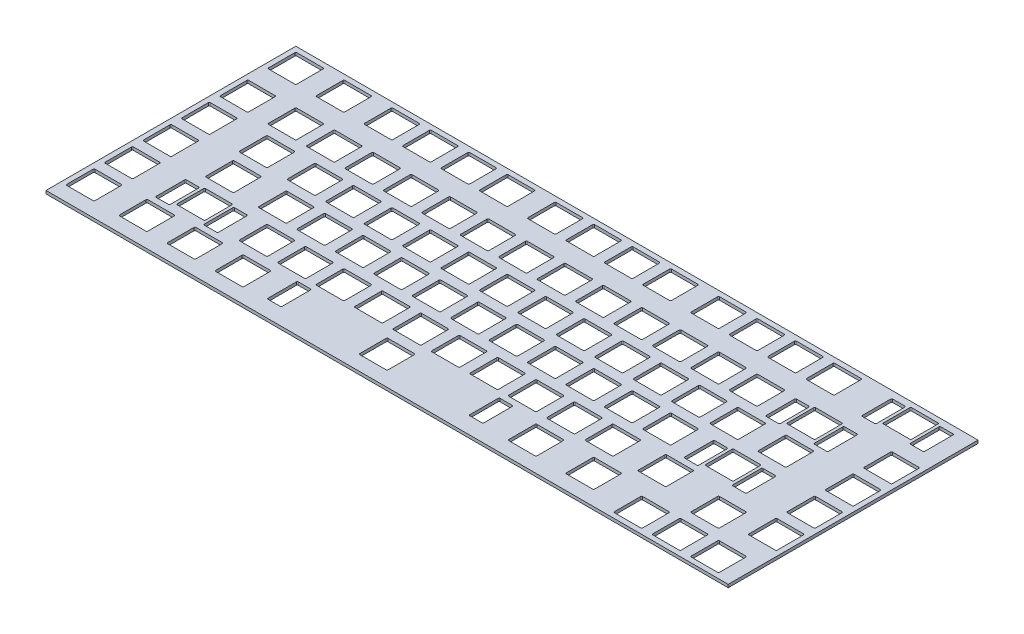
SolidWorks part; units mm, degrees
ref_plane "Front" through (0, 0, 0) normal (0, 0, 1) x (1, 0, 0)
ref_plane "Top" through (0, 0, 0) normal (0, 1, 0) x (1, 0, 0)
ref_plane "Right" through (0, 0, 0) normal (1, 0, 0) x (0, 0, -1)
sketch "Sketch1" plane through (0, 0, 0) normal (0, 1, 0) x (1, 0, 0)
  line L0 (3.025, -2.525) -> (16.025, -2.525)
  line L1 (3.025, -16.525) -> (16.025, -16.525)
  line L2 (2.525, -3.025) -> (2.525, -16.025)
  line L3 (16.525, -3.025) -> (16.525, -16.025)
  line L4 (26.8375, -2.525) -> (39.8375, -2.525)
  line L5 (26.8375, -16.525) -> (39.8375, -16.525)
  line L6 (26.3375, -3.025) -> (26.3375, -16.025)
  line L7 (40.3375, -3.025) -> (40.3375, -16.025)
  line L8 (50.65, -2.525) -> (63.65, -2.525)
  line L9 (50.65, -16.525) -> (63.65, -16.525)
  line L10 (50.15, -3.025) -> (50.15, -16.025)
  line L11 (64.15, -3.025) -> (64.15, -16.025)
  line L12 (69.7, -2.525) -> (82.7, -2.525)
  line L13 (69.7, -16.525) -> (82.7, -16.525)
  line L14 (69.2, -3.025) -> (69.2, -16.025)
  line L15 (83.2, -3.025) -> (83.2, -16.025)
  line L16 (88.75, -2.525) -> (101.75, -2.525)
  line L17 (88.75, -16.525) -> (101.75, -16.525)
  line L18 (88.25, -3.025) -> (88.25, -16.025)
  line L19 (102.25, -3.025) -> (102.25, -16.025)
  line L20 (107.8, -2.525) -> (120.8, -2.525)
  line L21 (107.8, -16.525) -> (120.8, -16.525)
  line L22 (107.3, -3.025) -> (107.3, -16.025)
  line L23 (121.3, -3.025) -> (121.3, -16.025)
  line L24 (131.6125, -2.525) -> (144.6125, -2.525)
  line L25 (131.6125, -16.525) -> (144.6125, -16.525)
  line L26 (131.1125, -3.025) -> (131.1125, -16.025)
  line L27 (145.1125, -3.025) -> (145.1125, -16.025)
  line L28 (150.6625, -2.525) -> (163.6625, -2.525)
  line L29 (150.6625, -16.525) -> (163.6625, -16.525)
  line L30 (150.1625, -3.025) -> (150.1625, -16.025)
  line L31 (164.1625, -3.025) -> (164.1625, -16.025)
  line L32 (169.7125, -2.525) -> (182.7125, -2.525)
  line L33 (169.7125, -16.525) -> (182.7125, -16.525)
  line L34 (169.2125, -3.025) -> (169.2125, -16.025)
  line L35 (183.2125, -3.025) -> (183.2125, -16.025)
  line L36 (188.7625, -2.525) -> (201.7625, -2.525)
  line L37 (188.7625, -16.525) -> (201.7625, -16.525)
  line L38 (188.2625, -3.025) -> (188.2625, -16.025)
  line L39 (202.2625, -3.025) -> (202.2625, -16.025)
  line L40 (212.575, -2.525) -> (225.575, -2.525)
  line L41 (212.575, -16.525) -> (225.575, -16.525)
  line L42 (212.075, -3.025) -> (212.075, -16.025)
  line L43 (226.075, -3.025) -> (226.075, -16.025)
  line L44 (231.625, -2.525) -> (244.625, -2.525)
  line L45 (231.625, -16.525) -> (244.625, -16.525)
  line L46 (231.125, -3.025) -> (231.125, -16.025)
  line L47 (245.125, -3.025) -> (245.125, -16.025)
  line L48 (250.675, -2.525) -> (263.675, -2.525)
  line L49 (250.675, -16.525) -> (263.675, -16.525)
  line L50 (250.175, -3.025) -> (250.175, -16.025)
  line L51 (264.175, -3.025) -> (264.175, -16.025)
  line L52 (269.725, -2.525) -> (282.725, -2.525)
  line L53 (269.725, -16.525) -> (282.725, -16.525)
  line L54 (269.225, -3.025) -> (269.225, -16.025)
  line L55 (283.225, -3.025) -> (283.225, -16.025)
  line L56 (307.825, -2.525) -> (320.825, -2.525)
  line L57 (307.825, -16.525) -> (320.825, -16.525)
  line L58 (307.325, -3.025) -> (307.325, -16.025)
  line L59 (321.325, -3.025) -> (321.325, -16.025)
  line L60 (299.387, -3.525) -> (305.387, -3.525)
  line L61 (299.387, -18.525) -> (305.387, -18.525)
  line L62 (298.887, -4.025) -> (298.887, -18.025)
  line L63 (305.887, -4.025) -> (305.887, -18.025)
  line L64 (323.263, -3.525) -> (329.263, -3.525)
  line L65 (323.263, -18.525) -> (329.263, -18.525)
  line L66 (322.763, -4.025) -> (322.763, -18.025)
  line L67 (329.763, -4.025) -> (329.763, -18.025)
  line L68 (3.025, -26.3375) -> (16.025, -26.3375)
  line L69 (3.025, -40.3375) -> (16.025, -40.3375)
  line L70 (2.525, -26.8375) -> (2.525, -39.8375)
  line L71 (16.525, -26.8375) -> (16.525, -39.8375)
  line L72 (26.8375, -26.3375) -> (39.8375, -26.3375)
  line L73 (26.8375, -40.3375) -> (39.8375, -40.3375)
  line L74 (26.3375, -26.8375) -> (26.3375, -39.8375)
  line L75 (40.3375, -26.8375) -> (40.3375, -39.8375)
  line L76 (45.8875, -26.3375) -> (58.8875, -26.3375)
  line L77 (45.8875, -40.3375) -> (58.8875, -40.3375)
  line L78 (45.3875, -26.8375) -> (45.3875, -39.8375)
  line L79 (59.3875, -26.8375) -> (59.3875, -39.8375)
  line L80 (64.9375, -26.3375) -> (77.9375, -26.3375)
  line L81 (64.9375, -40.3375) -> (77.9375, -40.3375)
  line L82 (64.4375, -26.8375) -> (64.4375, -39.8375)
  line L83 (78.4375, -26.8375) -> (78.4375, -39.8375)
  line L84 (83.9875, -26.3375) -> (96.9875, -26.3375)
  line L85 (83.9875, -40.3375) -> (96.9875, -40.3375)
  line L86 (83.4875, -26.8375) -> (83.4875, -39.8375)
  line L87 (97.4875, -26.8375) -> (97.4875, -39.8375)
  line L88 (103.0375, -26.3375) -> (116.0375, -26.3375)
  line L89 (103.0375, -40.3375) -> (116.0375, -40.3375)
  line L90 (102.5375, -26.8375) -> (102.5375, -39.8375)
  line L91 (116.5375, -26.8375) -> (116.5375, -39.8375)
  line L92 (122.0875, -26.3375) -> (135.0875, -26.3375)
  line L93 (122.0875, -40.3375) -> (135.0875, -40.3375)
  line L94 (121.5875, -26.8375) -> (121.5875, -39.8375)
  line L95 (135.5875, -26.8375) -> (135.5875, -39.8375)
  line L96 (141.1375, -26.3375) -> (154.1375, -26.3375)
  line L97 (141.1375, -40.3375) -> (154.1375, -40.3375)
  line L98 (140.6375, -26.8375) -> (140.6375, -39.8375)
  line L99 (154.6375, -26.8375) -> (154.6375, -39.8375)
  line L100 (160.1875, -26.3375) -> (173.1875, -26.3375)
  line L101 (160.1875, -40.3375) -> (173.1875, -40.3375)
  line L102 (159.6875, -26.8375) -> (159.6875, -39.8375)
  line L103 (173.6875, -26.8375) -> (173.6875, -39.8375)
  line L104 (179.2375, -26.3375) -> (192.2375, -26.3375)
  line L105 (179.2375, -40.3375) -> (192.2375, -40.3375)
  line L106 (178.7375, -26.8375) -> (178.7375, -39.8375)
  line L107 (192.7375, -26.8375) -> (192.7375, -39.8375)
  line L108 (198.2875, -26.3375) -> (211.2875, -26.3375)
  line L109 (198.2875, -40.3375) -> (211.2875, -40.3375)
  line L110 (197.7875, -26.8375) -> (197.7875, -39.8375)
  line L111 (211.7875, -26.8375) -> (211.7875, -39.8375)
  line L112 (217.3375, -26.3375) -> (230.3375, -26.3375)
  line L113 (217.3375, -40.3375) -> (230.3375, -40.3375)
  line L114 (216.8375, -26.8375) -> (216.8375, -39.8375)
  line L115 (230.8375, -26.8375) -> (230.8375, -39.8375)
  line L116 (236.3875, -26.3375) -> (249.3875, -26.3375)
  line L117 (236.3875, -40.3375) -> (249.3875, -40.3375)
  line L118 (235.8875, -26.8375) -> (235.8875, -39.8375)
  line L119 (249.8875, -26.8375) -> (249.8875, -39.8375)
  line L120 (255.4375, -26.3375) -> (268.4375, -26.3375)
  line L121 (255.4375, -40.3375) -> (268.4375, -40.3375)
  line L122 (254.9375, -26.8375) -> (254.9375, -39.8375)
  line L123 (268.9375, -26.8375) -> (268.9375, -39.8375)
  line L124 (284.0125, -26.3375) -> (297.0125, -26.3375)
  line L125 (284.0125, -40.3375) -> (297.0125, -40.3375)
  line L126 (283.5125, -26.8375) -> (283.5125, -39.8375)
  line L127 (297.5125, -26.8375) -> (297.5125, -39.8375)
  line L128 (275.5745, -27.3375) -> (281.5745, -27.3375)
  line L129 (275.5745, -42.3375) -> (281.5745, -42.3375)
  line L130 (275.0745, -27.8375) -> (275.0745, -41.8375)
  line L131 (282.0745, -27.8375) -> (282.0745, -41.8375)
  line L132 (299.4505, -27.3375) -> (305.4505, -27.3375)
  line L133 (299.4505, -42.3375) -> (305.4505, -42.3375)
  line L134 (298.9505, -27.8375) -> (298.9505, -41.8375)
  line L135 (305.9505, -27.8375) -> (305.9505, -41.8375)
  line L136 (322.1125, -26.3375) -> (335.1125, -26.3375)
  line L137 (322.1125, -40.3375) -> (335.1125, -40.3375)
  line L138 (321.6125, -26.8375) -> (321.6125, -39.8375)
  line L139 (335.6125, -26.8375) -> (335.6125, -39.8375)
  line L140 (3.025, -45.3875) -> (16.025, -45.3875)
  line L141 (3.025, -59.3875) -> (16.025, -59.3875)
  line L142 (2.525, -45.8875) -> (2.525, -58.8875)
  line L143 (16.525, -45.8875) -> (16.525, -58.8875)
  line L144 (31.6, -45.3875) -> (44.6, -45.3875)
  line L145 (31.6, -59.3875) -> (44.6, -59.3875)
  line L146 (31.1, -45.8875) -> (31.1, -58.8875)
  line L147 (45.1, -45.8875) -> (45.1, -58.8875)
  line L148 (55.4125, -45.3875) -> (68.4125, -45.3875)
  line L149 (55.4125, -59.3875) -> (68.4125, -59.3875)
  line L150 (54.9125, -45.8875) -> (54.9125, -58.8875)
  line L151 (68.9125, -45.8875) -> (68.9125, -58.8875)
  line L152 (74.4625, -45.3875) -> (87.4625, -45.3875)
  line L153 (74.4625, -59.3875) -> (87.4625, -59.3875)
  line L154 (73.9625, -45.8875) -> (73.9625, -58.8875)
  line L155 (87.9625, -45.8875) -> (87.9625, -58.8875)
  line L156 (93.5125, -45.3875) -> (106.5125, -45.3875)
  line L157 (93.5125, -59.3875) -> (106.5125, -59.3875)
  line L158 (93.0125, -45.8875) -> (93.0125, -58.8875)
  line L159 (107.0125, -45.8875) -> (107.0125, -58.8875)
  line L160 (112.5625, -45.3875) -> (125.5625, -45.3875)
  line L161 (112.5625, -59.3875) -> (125.5625, -59.3875)
  line L162 (112.0625, -45.8875) -> (112.0625, -58.8875)
  line L163 (126.0625, -45.8875) -> (126.0625, -58.8875)
  line L164 (131.6125, -45.3875) -> (144.6125, -45.3875)
  line L165 (131.6125, -59.3875) -> (144.6125, -59.3875)
  line L166 (131.1125, -45.8875) -> (131.1125, -58.8875)
  line L167 (145.1125, -45.8875) -> (145.1125, -58.8875)
  line L168 (150.6625, -45.3875) -> (163.6625, -45.3875)
  line L169 (150.6625, -59.3875) -> (163.6625, -59.3875)
  line L170 (150.1625, -45.8875) -> (150.1625, -58.8875)
  line L171 (164.1625, -45.8875) -> (164.1625, -58.8875)
  line L172 (169.7125, -45.3875) -> (182.7125, -45.3875)
  line L173 (169.7125, -59.3875) -> (182.7125, -59.3875)
  line L174 (169.2125, -45.8875) -> (169.2125, -58.8875)
  line L175 (183.2125, -45.8875) -> (183.2125, -58.8875)
  line L176 (188.7625, -45.3875) -> (201.7625, -45.3875)
  line L177 (188.7625, -59.3875) -> (201.7625, -59.3875)
  line L178 (188.2625, -45.8875) -> (188.2625, -58.8875)
  line L179 (202.2625, -45.8875) -> (202.2625, -58.8875)
  line L180 (207.8125, -45.3875) -> (220.8125, -45.3875)
  line L181 (207.8125, -59.3875) -> (220.8125, -59.3875)
  line L182 (207.3125, -45.8875) -> (207.3125, -58.8875)
  line L183 (221.3125, -45.8875) -> (221.3125, -58.8875)
  line L184 (226.8625, -45.3875) -> (239.8625, -45.3875)
  line L185 (226.8625, -59.3875) -> (239.8625, -59.3875)
  line L186 (226.3625, -45.8875) -> (226.3625, -58.8875)
  line L187 (240.3625, -45.8875) -> (240.3625, -58.8875)
  line L188 (245.9125, -45.3875) -> (258.9125, -45.3875)
  line L189 (245.9125, -59.3875) -> (258.9125, -59.3875)
  line L190 (245.4125, -45.8875) -> (245.4125, -58.8875)
  line L191 (259.4125, -45.8875) -> (259.4125, -58.8875)
  line L192 (264.9625, -45.3875) -> (277.9625, -45.3875)
  line L193 (264.9625, -59.3875) -> (277.9625, -59.3875)
  line L194 (264.4625, -45.8875) -> (264.4625, -58.8875)
  line L195 (278.4625, -45.8875) -> (278.4625, -58.8875)
  line L196 (288.775, -45.3875) -> (301.775, -45.3875)
  line L197 (288.775, -59.3875) -> (301.775, -59.3875)
  line L198 (288.275, -45.8875) -> (288.275, -58.8875)
  line L199 (302.275, -45.8875) -> (302.275, -58.8875)
  line L200 (322.1125, -45.3875) -> (335.1125, -45.3875)
  line L201 (322.1125, -59.3875) -> (335.1125, -59.3875)
  line L202 (321.6125, -45.8875) -> (321.6125, -58.8875)
  line L203 (335.6125, -45.8875) -> (335.6125, -58.8875)
  line L204 (3.025, -64.4375) -> (16.025, -64.4375)
  line L205 (3.025, -78.4375) -> (16.025, -78.4375)
  line L206 (2.525, -64.9375) -> (2.525, -77.9375)
  line L207 (16.525, -64.9375) -> (16.525, -77.9375)
  line L208 (33.9813, -64.4375) -> (46.9813, -64.4375)
  line L209 (33.9813, -78.4375) -> (46.9813, -78.4375)
  line L210 (33.4813, -64.9375) -> (33.4813, -77.9375)
  line L211 (47.4813, -64.9375) -> (47.4813, -77.9375)
  line L212 (60.175, -64.4375) -> (73.175, -64.4375)
  line L213 (60.175, -78.4375) -> (73.175, -78.4375)
  line L214 (59.675, -64.9375) -> (59.675, -77.9375)
  line L215 (73.675, -64.9375) -> (73.675, -77.9375)
  line L216 (79.225, -64.4375) -> (92.225, -64.4375)
  line L217 (79.225, -78.4375) -> (92.225, -78.4375)
  line L218 (78.725, -64.9375) -> (78.725, -77.9375)
  line L219 (92.725, -64.9375) -> (92.725, -77.9375)
  line L220 (98.275, -64.4375) -> (111.275, -64.4375)
  line L221 (98.275, -78.4375) -> (111.275, -78.4375)
  line L222 (97.775, -64.9375) -> (97.775, -77.9375)
  line L223 (111.775, -64.9375) -> (111.775, -77.9375)
  line L224 (117.325, -64.4375) -> (130.325, -64.4375)
  line L225 (117.325, -78.4375) -> (130.325, -78.4375)
  line L226 (116.825, -64.9375) -> (116.825, -77.9375)
  line L227 (130.825, -64.9375) -> (130.825, -77.9375)
  line L228 (136.375, -64.4375) -> (149.375, -64.4375)
  line L229 (136.375, -78.4375) -> (149.375, -78.4375)
  line L230 (135.875, -64.9375) -> (135.875, -77.9375)
  line L231 (149.875, -64.9375) -> (149.875, -77.9375)
  line L232 (155.425, -64.4375) -> (168.425, -64.4375)
  line L233 (155.425, -78.4375) -> (168.425, -78.4375)
  line L234 (154.925, -64.9375) -> (154.925, -77.9375)
  line L235 (168.925, -64.9375) -> (168.925, -77.9375)
  line L236 (174.475, -64.4375) -> (187.475, -64.4375)
  line L237 (174.475, -78.4375) -> (187.475, -78.4375)
  line L238 (173.975, -64.9375) -> (173.975, -77.9375)
  line L239 (187.975, -64.9375) -> (187.975, -77.9375)
  line L240 (193.525, -64.4375) -> (206.525, -64.4375)
  line L241 (193.525, -78.4375) -> (206.525, -78.4375)
  line L242 (193.025, -64.9375) -> (193.025, -77.9375)
  line L243 (207.025, -64.9375) -> (207.025, -77.9375)
  line L244 (212.575, -64.4375) -> (225.575, -64.4375)
  line L245 (212.575, -78.4375) -> (225.575, -78.4375)
  line L246 (212.075, -64.9375) -> (212.075, -77.9375)
  line L247 (226.075, -64.9375) -> (226.075, -77.9375)
  line L248 (231.625, -64.4375) -> (244.625, -64.4375)
  line L249 (231.625, -78.4375) -> (244.625, -78.4375)
  line L250 (231.125, -64.9375) -> (231.125, -77.9375)
  line L251 (245.125, -64.9375) -> (245.125, -77.9375)
  line L252 (250.675, -64.4375) -> (263.675, -64.4375)
  line L253 (250.675, -78.4375) -> (263.675, -78.4375)
  line L254 (250.175, -64.9375) -> (250.175, -77.9375)
  line L255 (264.175, -64.9375) -> (264.175, -77.9375)
  line L256 (281.6313, -64.4375) -> (294.6313, -64.4375)
  line L257 (281.6313, -78.4375) -> (294.6313, -78.4375)
  line L258 (281.1313, -64.9375) -> (281.1313, -77.9375)
  line L259 (295.1313, -64.9375) -> (295.1313, -77.9375)
  line L260 (273.1932, -65.4375) -> (279.1932, -65.4375)
  line L261 (273.1932, -80.4375) -> (279.1932, -80.4375)
  line L262 (272.6932, -65.9375) -> (272.6932, -79.9375)
  line L263 (279.6932, -65.9375) -> (279.6932, -79.9375)
  line L264 (297.0693, -65.4375) -> (303.0693, -65.4375)
  line L265 (297.0693, -80.4375) -> (303.0693, -80.4375)
  line L266 (296.5693, -65.9375) -> (296.5693, -79.9375)
  line L267 (303.5693, -65.9375) -> (303.5693, -79.9375)
  line L268 (322.1125, -64.4375) -> (335.1125, -64.4375)
  line L269 (322.1125, -78.4375) -> (335.1125, -78.4375)
  line L270 (321.6125, -64.9375) -> (321.6125, -77.9375)
  line L271 (335.6125, -64.9375) -> (335.6125, -77.9375)
  line L272 (3.025, -83.4875) -> (16.025, -83.4875)
  line L273 (3.025, -97.4875) -> (16.025, -97.4875)
  line L274 (2.525, -83.9875) -> (2.525, -96.9875)
  line L275 (16.525, -83.9875) -> (16.525, -96.9875)
  line L276 (38.7437, -83.4875) -> (51.7437, -83.4875)
  line L277 (38.7437, -97.4875) -> (51.7437, -97.4875)
  line L278 (38.2437, -83.9875) -> (38.2437, -96.9875)
  line L279 (52.2437, -83.9875) -> (52.2437, -96.9875)
  line L280 (30.3057, -84.4875) -> (36.3058, -84.4875)
  line L281 (30.3057, -99.4875) -> (36.3058, -99.4875)
  line L282 (29.8057, -84.9875) -> (29.8057, -98.9875)
  line L283 (36.8058, -84.9875) -> (36.8058, -98.9875)
  line L284 (54.1818, -84.4875) -> (60.1818, -84.4875)
  line L285 (54.1818, -99.4875) -> (60.1818, -99.4875)
  line L286 (53.6818, -84.9875) -> (53.6818, -98.9875)
  line L287 (60.6818, -84.9875) -> (60.6818, -98.9875)
  line L288 (69.7, -83.4875) -> (82.7, -83.4875)
  line L289 (69.7, -97.4875) -> (82.7, -97.4875)
  line L290 (69.2, -83.9875) -> (69.2, -96.9875)
  line L291 (83.2, -83.9875) -> (83.2, -96.9875)
  line L292 (88.75, -83.4875) -> (101.75, -83.4875)
  line L293 (88.75, -97.4875) -> (101.75, -97.4875)
  line L294 (88.25, -83.9875) -> (88.25, -96.9875)
  line L295 (102.25, -83.9875) -> (102.25, -96.9875)
  line L296 (107.8, -83.4875) -> (120.8, -83.4875)
  line L297 (107.8, -97.4875) -> (120.8, -97.4875)
  line L298 (107.3, -83.9875) -> (107.3, -96.9875)
  line L299 (121.3, -83.9875) -> (121.3, -96.9875)
  line L300 (126.85, -83.4875) -> (139.85, -83.4875)
  line L301 (126.85, -97.4875) -> (139.85, -97.4875)
  line L302 (126.35, -83.9875) -> (126.35, -96.9875)
  line L303 (140.35, -83.9875) -> (140.35, -96.9875)
  line L304 (145.9, -83.4875) -> (158.9, -83.4875)
  line L305 (145.9, -97.4875) -> (158.9, -97.4875)
  line L306 (145.4, -83.9875) -> (145.4, -96.9875)
  line L307 (159.4, -83.9875) -> (159.4, -96.9875)
  line L308 (164.95, -83.4875) -> (177.95, -83.4875)
  line L309 (164.95, -97.4875) -> (177.95, -97.4875)
  line L310 (164.45, -83.9875) -> (164.45, -96.9875)
  line L311 (178.45, -83.9875) -> (178.45, -96.9875)
  line L312 (184, -83.4875) -> (197, -83.4875)
  line L313 (184, -97.4875) -> (197, -97.4875)
  line L314 (183.5, -83.9875) -> (183.5, -96.9875)
  line L315 (197.5, -83.9875) -> (197.5, -96.9875)
  line L316 (203.05, -83.4875) -> (216.05, -83.4875)
  line L317 (203.05, -97.4875) -> (216.05, -97.4875)
  line L318 (202.55, -83.9875) -> (202.55, -96.9875)
  line L319 (216.55, -83.9875) -> (216.55, -96.9875)
  line L320 (222.1, -83.4875) -> (235.1, -83.4875)
  line L321 (222.1, -97.4875) -> (235.1, -97.4875)
  line L322 (221.6, -83.9875) -> (221.6, -96.9875)
  line L323 (235.6, -83.9875) -> (235.6, -96.9875)
  line L324 (241.15, -83.4875) -> (254.15, -83.4875)
  line L325 (241.15, -97.4875) -> (254.15, -97.4875)
  line L326 (240.65, -83.9875) -> (240.65, -96.9875)
  line L327 (254.65, -83.9875) -> (254.65, -96.9875)
  line L328 (267.3438, -83.4875) -> (280.3438, -83.4875)
  line L329 (267.3438, -97.4875) -> (280.3438, -97.4875)
  line L330 (266.8438, -83.9875) -> (266.8438, -96.9875)
  line L331 (280.8438, -83.9875) -> (280.8438, -96.9875)
  line L332 (322.1125, -83.4875) -> (335.1125, -83.4875)
  line L333 (322.1125, -97.4875) -> (335.1125, -97.4875)
  line L334 (321.6125, -83.9875) -> (321.6125, -96.9875)
  line L335 (335.6125, -83.9875) -> (335.6125, -96.9875)
  line L336 (298.3, -88.25) -> (311.3, -88.25)
  line L337 (298.3, -102.25) -> (311.3, -102.25)
  line L338 (297.8, -88.75) -> (297.8, -101.75)
  line L339 (311.8, -88.75) -> (311.8, -101.75)
  line L340 (3.025, -102.5375) -> (16.025, -102.5375)
  line L341 (3.025, -116.5375) -> (16.025, -116.5375)
  line L342 (2.525, -103.0375) -> (2.525, -116.0375)
  line L343 (16.525, -103.0375) -> (16.525, -116.0375)
  line L344 (29.2188, -102.5375) -> (42.2188, -102.5375)
  line L345 (29.2188, -116.5375) -> (42.2188, -116.5375)
  line L346 (28.7188, -103.0375) -> (28.7188, -116.0375)
  line L347 (42.7188, -103.0375) -> (42.7188, -116.0375)
  line L348 (53.0312, -102.5375) -> (66.0312, -102.5375)
  line L349 (53.0312, -116.5375) -> (66.0312, -116.5375)
  line L350 (52.5312, -103.0375) -> (52.5312, -116.0375)
  line L351 (66.5312, -103.0375) -> (66.5312, -116.0375)
  line L352 (76.8438, -102.5375) -> (89.8438, -102.5375)
  line L353 (76.8438, -116.5375) -> (89.8438, -116.5375)
  line L354 (76.3438, -103.0375) -> (76.3438, -116.0375)
  line L355 (90.3438, -103.0375) -> (90.3438, -116.0375)
  line L356 (148.2812, -102.5375) -> (161.2813, -102.5375)
  line L357 (148.2812, -116.5375) -> (161.2813, -116.5375)
  line L358 (147.7812, -103.0375) -> (147.7812, -116.0375)
  line L359 (161.7813, -103.0375) -> (161.7813, -116.0375)
  line L360 (207.7812, -115.5375) -> (201.7812, -115.5375)
  line L361 (207.7812, -100.5375) -> (201.7812, -100.5375)
  line L362 (208.2812, -115.0375) -> (208.2812, -101.0375)
  line L363 (201.2812, -115.0375) -> (201.2812, -101.0375)
  line L364 (107.7813, -115.5375) -> (101.7812, -115.5375)
  line L365 (107.7813, -100.5375) -> (101.7812, -100.5375)
  line L366 (108.2812, -115.0375) -> (108.2812, -101.0375)
  line L367 (101.2812, -115.0375) -> (101.2812, -101.0375)
  line L368 (222.1, -102.5375) -> (235.1, -102.5375)
  line L369 (222.1, -116.5375) -> (235.1, -116.5375)
  line L370 (221.6, -103.0375) -> (221.6, -116.0375)
  line L371 (235.6, -103.0375) -> (235.6, -116.0375)
  line L372 (250.675, -102.5375) -> (263.675, -102.5375)
  line L373 (250.675, -116.5375) -> (263.675, -116.5375)
  line L374 (250.175, -103.0375) -> (250.175, -116.0375)
  line L375 (264.175, -103.0375) -> (264.175, -116.0375)
  line L376 (279.25, -107.3) -> (292.25, -107.3)
  line L377 (279.25, -121.3) -> (292.25, -121.3)
  line L378 (278.75, -107.8) -> (278.75, -120.8)
  line L379 (292.75, -107.8) -> (292.75, -120.8)
  line L380 (298.3, -107.3) -> (311.3, -107.3)
  line L381 (298.3, -121.3) -> (311.3, -121.3)
  line L382 (297.8, -107.8) -> (297.8, -120.8)
  line L383 (311.8, -107.8) -> (311.8, -120.8)
  line L384 (317.35, -107.3) -> (330.35, -107.3)
  line L385 (317.35, -121.3) -> (330.35, -121.3)
  line L386 (316.85, -107.8) -> (316.85, -120.8)
  line L387 (330.85, -107.8) -> (330.85, -120.8)
  line L388 (0, -123.825) -> (338.1375, -123.825)
  line L389 (0, 0) -> (338.1375, 0)
  line L390 (0, -123.825) -> (0, 0)
  line L391 (338.1375, -123.825) -> (338.1375, 0)
  arc A0 (3.025, -2.525) -> (2.525, -3.025) centre (3.025, -3.025) ccw
  arc A1 (16.525, -3.025) -> (16.025, -2.525) centre (16.025, -3.025) ccw
  arc A2 (2.525, -16.025) -> (3.025, -16.525) centre (3.025, -16.025) ccw
  arc A3 (16.025, -16.525) -> (16.525, -16.025) centre (16.025, -16.025) ccw
  arc A4 (26.8375, -2.525) -> (26.3375, -3.025) centre (26.8375, -3.025) ccw
  arc A5 (40.3375, -3.025) -> (39.8375, -2.525) centre (39.8375, -3.025) ccw
  arc A6 (26.3375, -16.025) -> (26.8375, -16.525) centre (26.8375, -16.025) ccw
  arc A7 (39.8375, -16.525) -> (40.3375, -16.025) centre (39.8375, -16.025) ccw
  arc A8 (50.65, -2.525) -> (50.15, -3.025) centre (50.65, -3.025) ccw
  arc A9 (64.15, -3.025) -> (63.65, -2.525) centre (63.65, -3.025) ccw
  arc A10 (50.15, -16.025) -> (50.65, -16.525) centre (50.65, -16.025) ccw
  arc A11 (63.65, -16.525) -> (64.15, -16.025) centre (63.65, -16.025) ccw
  arc A12 (69.7, -2.525) -> (69.2, -3.025) centre (69.7, -3.025) ccw
  arc A13 (83.2, -3.025) -> (82.7, -2.525) centre (82.7, -3.025) ccw
  arc A14 (69.2, -16.025) -> (69.7, -16.525) centre (69.7, -16.025) ccw
  arc A15 (82.7, -16.525) -> (83.2, -16.025) centre (82.7, -16.025) ccw
  arc A16 (88.75, -2.525) -> (88.25, -3.025) centre (88.75, -3.025) ccw
  arc A17 (102.25, -3.025) -> (101.75, -2.525) centre (101.75, -3.025) ccw
  arc A18 (88.25, -16.025) -> (88.75, -16.525) centre (88.75, -16.025) ccw
  arc A19 (101.75, -16.525) -> (102.25, -16.025) centre (101.75, -16.025) ccw
  arc A20 (107.8, -2.525) -> (107.3, -3.025) centre (107.8, -3.025) ccw
  arc A21 (121.3, -3.025) -> (120.8, -2.525) centre (120.8, -3.025) ccw
  arc A22 (107.3, -16.025) -> (107.8, -16.525) centre (107.8, -16.025) ccw
  arc A23 (120.8, -16.525) -> (121.3, -16.025) centre (120.8, -16.025) ccw
  arc A24 (131.6125, -2.525) -> (131.1125, -3.025) centre (131.6125, -3.025) ccw
  arc A25 (145.1125, -3.025) -> (144.6125, -2.525) centre (144.6125, -3.025) ccw
  arc A26 (131.1125, -16.025) -> (131.6125, -16.525) centre (131.6125, -16.025) ccw
  arc A27 (144.6125, -16.525) -> (145.1125, -16.025) centre (144.6125, -16.025) ccw
  arc A28 (150.6625, -2.525) -> (150.1625, -3.025) centre (150.6625, -3.025) ccw
  arc A29 (164.1625, -3.025) -> (163.6625, -2.525) centre (163.6625, -3.025) ccw
  arc A30 (150.1625, -16.025) -> (150.6625, -16.525) centre (150.6625, -16.025) ccw
  arc A31 (163.6625, -16.525) -> (164.1625, -16.025) centre (163.6625, -16.025) ccw
  arc A32 (169.7125, -2.525) -> (169.2125, -3.025) centre (169.7125, -3.025) ccw
  arc A33 (183.2125, -3.025) -> (182.7125, -2.525) centre (182.7125, -3.025) ccw
  arc A34 (169.2125, -16.025) -> (169.7125, -16.525) centre (169.7125, -16.025) ccw
  arc A35 (182.7125, -16.525) -> (183.2125, -16.025) centre (182.7125, -16.025) ccw
  arc A36 (188.7625, -2.525) -> (188.2625, -3.025) centre (188.7625, -3.025) ccw
  arc A37 (202.2625, -3.025) -> (201.7625, -2.525) centre (201.7625, -3.025) ccw
  arc A38 (188.2625, -16.025) -> (188.7625, -16.525) centre (188.7625, -16.025) ccw
  arc A39 (201.7625, -16.525) -> (202.2625, -16.025) centre (201.7625, -16.025) ccw
  arc A40 (212.575, -2.525) -> (212.075, -3.025) centre (212.575, -3.025) ccw
  arc A41 (226.075, -3.025) -> (225.575, -2.525) centre (225.575, -3.025) ccw
  arc A42 (212.075, -16.025) -> (212.575, -16.525) centre (212.575, -16.025) ccw
  arc A43 (225.575, -16.525) -> (226.075, -16.025) centre (225.575, -16.025) ccw
  arc A44 (231.625, -2.525) -> (231.125, -3.025) centre (231.625, -3.025) ccw
  arc A45 (245.125, -3.025) -> (244.625, -2.525) centre (244.625, -3.025) ccw
  arc A46 (231.125, -16.025) -> (231.625, -16.525) centre (231.625, -16.025) ccw
  arc A47 (244.625, -16.525) -> (245.125, -16.025) centre (244.625, -16.025) ccw
  arc A48 (250.675, -2.525) -> (250.175, -3.025) centre (250.675, -3.025) ccw
  arc A49 (264.175, -3.025) -> (263.675, -2.525) centre (263.675, -3.025) ccw
  arc A50 (250.175, -16.025) -> (250.675, -16.525) centre (250.675, -16.025) ccw
  arc A51 (263.675, -16.525) -> (264.175, -16.025) centre (263.675, -16.025) ccw
  arc A52 (269.725, -2.525) -> (269.225, -3.025) centre (269.725, -3.025) ccw
  arc A53 (283.225, -3.025) -> (282.725, -2.525) centre (282.725, -3.025) ccw
  arc A54 (269.225, -16.025) -> (269.725, -16.525) centre (269.725, -16.025) ccw
  arc A55 (282.725, -16.525) -> (283.225, -16.025) centre (282.725, -16.025) ccw
  arc A56 (307.825, -2.525) -> (307.325, -3.025) centre (307.825, -3.025) ccw
  arc A57 (321.325, -3.025) -> (320.825, -2.525) centre (320.825, -3.025) ccw
  arc A58 (307.325, -16.025) -> (307.825, -16.525) centre (307.825, -16.025) ccw
  arc A59 (320.825, -16.525) -> (321.325, -16.025) centre (320.825, -16.025) ccw
  arc A60 (299.387, -3.525) -> (298.887, -4.025) centre (299.387, -4.025) ccw
  arc A61 (305.887, -4.025) -> (305.387, -3.525) centre (305.387, -4.025) ccw
  arc A62 (298.887, -18.025) -> (299.387, -18.525) centre (299.387, -18.025) ccw
  arc A63 (305.387, -18.525) -> (305.887, -18.025) centre (305.387, -18.025) ccw
  arc A64 (323.263, -3.525) -> (322.763, -4.025) centre (323.263, -4.025) ccw
  arc A65 (329.763, -4.025) -> (329.263, -3.525) centre (329.263, -4.025) ccw
  arc A66 (322.763, -18.025) -> (323.263, -18.525) centre (323.263, -18.025) ccw
  arc A67 (329.263, -18.525) -> (329.763, -18.025) centre (329.263, -18.025) ccw
  arc A68 (3.025, -26.3375) -> (2.525, -26.8375) centre (3.025, -26.8375) ccw
  arc A69 (16.525, -26.8375) -> (16.025, -26.3375) centre (16.025, -26.8375) ccw
  arc A70 (2.525, -39.8375) -> (3.025, -40.3375) centre (3.025, -39.8375) ccw
  arc A71 (16.025, -40.3375) -> (16.525, -39.8375) centre (16.025, -39.8375) ccw
  arc A72 (26.8375, -26.3375) -> (26.3375, -26.8375) centre (26.8375, -26.8375) ccw
  arc A73 (40.3375, -26.8375) -> (39.8375, -26.3375) centre (39.8375, -26.8375) ccw
  arc A74 (26.3375, -39.8375) -> (26.8375, -40.3375) centre (26.8375, -39.8375) ccw
  arc A75 (39.8375, -40.3375) -> (40.3375, -39.8375) centre (39.8375, -39.8375) ccw
  arc A76 (45.8875, -26.3375) -> (45.3875, -26.8375) centre (45.8875, -26.8375) ccw
  arc A77 (59.3875, -26.8375) -> (58.8875, -26.3375) centre (58.8875, -26.8375) ccw
  arc A78 (45.3875, -39.8375) -> (45.8875, -40.3375) centre (45.8875, -39.8375) ccw
  arc A79 (58.8875, -40.3375) -> (59.3875, -39.8375) centre (58.8875, -39.8375) ccw
  arc A80 (64.9375, -26.3375) -> (64.4375, -26.8375) centre (64.9375, -26.8375) ccw
  arc A81 (78.4375, -26.8375) -> (77.9375, -26.3375) centre (77.9375, -26.8375) ccw
  arc A82 (64.4375, -39.8375) -> (64.9375, -40.3375) centre (64.9375, -39.8375) ccw
  arc A83 (77.9375, -40.3375) -> (78.4375, -39.8375) centre (77.9375, -39.8375) ccw
  arc A84 (83.9875, -26.3375) -> (83.4875, -26.8375) centre (83.9875, -26.8375) ccw
  arc A85 (97.4875, -26.8375) -> (96.9875, -26.3375) centre (96.9875, -26.8375) ccw
  arc A86 (83.4875, -39.8375) -> (83.9875, -40.3375) centre (83.9875, -39.8375) ccw
  arc A87 (96.9875, -40.3375) -> (97.4875, -39.8375) centre (96.9875, -39.8375) ccw
  arc A88 (103.0375, -26.3375) -> (102.5375, -26.8375) centre (103.0375, -26.8375) ccw
  arc A89 (116.5375, -26.8375) -> (116.0375, -26.3375) centre (116.0375, -26.8375) ccw
  arc A90 (102.5375, -39.8375) -> (103.0375, -40.3375) centre (103.0375, -39.8375) ccw
  arc A91 (116.0375, -40.3375) -> (116.5375, -39.8375) centre (116.0375, -39.8375) ccw
  arc A92 (122.0875, -26.3375) -> (121.5875, -26.8375) centre (122.0875, -26.8375) ccw
  arc A93 (135.5875, -26.8375) -> (135.0875, -26.3375) centre (135.0875, -26.8375) ccw
  arc A94 (121.5875, -39.8375) -> (122.0875, -40.3375) centre (122.0875, -39.8375) ccw
  arc A95 (135.0875, -40.3375) -> (135.5875, -39.8375) centre (135.0875, -39.8375) ccw
  arc A96 (141.1375, -26.3375) -> (140.6375, -26.8375) centre (141.1375, -26.8375) ccw
  arc A97 (154.6375, -26.8375) -> (154.1375, -26.3375) centre (154.1375, -26.8375) ccw
  arc A98 (140.6375, -39.8375) -> (141.1375, -40.3375) centre (141.1375, -39.8375) ccw
  arc A99 (154.1375, -40.3375) -> (154.6375, -39.8375) centre (154.1375, -39.8375) ccw
  arc A100 (160.1875, -26.3375) -> (159.6875, -26.8375) centre (160.1875, -26.8375) ccw
  arc A101 (173.6875, -26.8375) -> (173.1875, -26.3375) centre (173.1875, -26.8375) ccw
  arc A102 (159.6875, -39.8375) -> (160.1875, -40.3375) centre (160.1875, -39.8375) ccw
  arc A103 (173.1875, -40.3375) -> (173.6875, -39.8375) centre (173.1875, -39.8375) ccw
  arc A104 (179.2375, -26.3375) -> (178.7375, -26.8375) centre (179.2375, -26.8375) ccw
  arc A105 (192.7375, -26.8375) -> (192.2375, -26.3375) centre (192.2375, -26.8375) ccw
  arc A106 (178.7375, -39.8375) -> (179.2375, -40.3375) centre (179.2375, -39.8375) ccw
  arc A107 (192.2375, -40.3375) -> (192.7375, -39.8375) centre (192.2375, -39.8375) ccw
  arc A108 (198.2875, -26.3375) -> (197.7875, -26.8375) centre (198.2875, -26.8375) ccw
  arc A109 (211.7875, -26.8375) -> (211.2875, -26.3375) centre (211.2875, -26.8375) ccw
  arc A110 (197.7875, -39.8375) -> (198.2875, -40.3375) centre (198.2875, -39.8375) ccw
  arc A111 (211.2875, -40.3375) -> (211.7875, -39.8375) centre (211.2875, -39.8375) ccw
  arc A112 (217.3375, -26.3375) -> (216.8375, -26.8375) centre (217.3375, -26.8375) ccw
  arc A113 (230.8375, -26.8375) -> (230.3375, -26.3375) centre (230.3375, -26.8375) ccw
  arc A114 (216.8375, -39.8375) -> (217.3375, -40.3375) centre (217.3375, -39.8375) ccw
  arc A115 (230.3375, -40.3375) -> (230.8375, -39.8375) centre (230.3375, -39.8375) ccw
  arc A116 (236.3875, -26.3375) -> (235.8875, -26.8375) centre (236.3875, -26.8375) ccw
  arc A117 (249.8875, -26.8375) -> (249.3875, -26.3375) centre (249.3875, -26.8375) ccw
  arc A118 (235.8875, -39.8375) -> (236.3875, -40.3375) centre (236.3875, -39.8375) ccw
  arc A119 (249.3875, -40.3375) -> (249.8875, -39.8375) centre (249.3875, -39.8375) ccw
  arc A120 (255.4375, -26.3375) -> (254.9375, -26.8375) centre (255.4375, -26.8375) ccw
  arc A121 (268.9375, -26.8375) -> (268.4375, -26.3375) centre (268.4375, -26.8375) ccw
  arc A122 (254.9375, -39.8375) -> (255.4375, -40.3375) centre (255.4375, -39.8375) ccw
  arc A123 (268.4375, -40.3375) -> (268.9375, -39.8375) centre (268.4375, -39.8375) ccw
  arc A124 (284.0125, -26.3375) -> (283.5125, -26.8375) centre (284.0125, -26.8375) ccw
  arc A125 (297.5125, -26.8375) -> (297.0125, -26.3375) centre (297.0125, -26.8375) ccw
  arc A126 (283.5125, -39.8375) -> (284.0125, -40.3375) centre (284.0125, -39.8375) ccw
  arc A127 (297.0125, -40.3375) -> (297.5125, -39.8375) centre (297.0125, -39.8375) ccw
  arc A128 (275.5745, -27.3375) -> (275.0745, -27.8375) centre (275.5745, -27.8375) ccw
  arc A129 (282.0745, -27.8375) -> (281.5745, -27.3375) centre (281.5745, -27.8375) ccw
  arc A130 (275.0745, -41.8375) -> (275.5745, -42.3375) centre (275.5745, -41.8375) ccw
  arc A131 (281.5745, -42.3375) -> (282.0745, -41.8375) centre (281.5745, -41.8375) ccw
  arc A132 (299.4505, -27.3375) -> (298.9505, -27.8375) centre (299.4505, -27.8375) ccw
  arc A133 (305.9505, -27.8375) -> (305.4505, -27.3375) centre (305.4505, -27.8375) ccw
  arc A134 (298.9505, -41.8375) -> (299.4505, -42.3375) centre (299.4505, -41.8375) ccw
  arc A135 (305.4505, -42.3375) -> (305.9505, -41.8375) centre (305.4505, -41.8375) ccw
  arc A136 (322.1125, -26.3375) -> (321.6125, -26.8375) centre (322.1125, -26.8375) ccw
  arc A137 (335.6125, -26.8375) -> (335.1125, -26.3375) centre (335.1125, -26.8375) ccw
  arc A138 (321.6125, -39.8375) -> (322.1125, -40.3375) centre (322.1125, -39.8375) ccw
  arc A139 (335.1125, -40.3375) -> (335.6125, -39.8375) centre (335.1125, -39.8375) ccw
  arc A140 (3.025, -45.3875) -> (2.525, -45.8875) centre (3.025, -45.8875) ccw
  arc A141 (16.525, -45.8875) -> (16.025, -45.3875) centre (16.025, -45.8875) ccw
  arc A142 (2.525, -58.8875) -> (3.025, -59.3875) centre (3.025, -58.8875) ccw
  arc A143 (16.025, -59.3875) -> (16.525, -58.8875) centre (16.025, -58.8875) ccw
  arc A144 (31.6, -45.3875) -> (31.1, -45.8875) centre (31.6, -45.8875) ccw
  arc A145 (45.1, -45.8875) -> (44.6, -45.3875) centre (44.6, -45.8875) ccw
  arc A146 (31.1, -58.8875) -> (31.6, -59.3875) centre (31.6, -58.8875) ccw
  arc A147 (44.6, -59.3875) -> (45.1, -58.8875) centre (44.6, -58.8875) ccw
  arc A148 (55.4125, -45.3875) -> (54.9125, -45.8875) centre (55.4125, -45.8875) ccw
  arc A149 (68.9125, -45.8875) -> (68.4125, -45.3875) centre (68.4125, -45.8875) ccw
  arc A150 (54.9125, -58.8875) -> (55.4125, -59.3875) centre (55.4125, -58.8875) ccw
  arc A151 (68.4125, -59.3875) -> (68.9125, -58.8875) centre (68.4125, -58.8875) ccw
  arc A152 (74.4625, -45.3875) -> (73.9625, -45.8875) centre (74.4625, -45.8875) ccw
  arc A153 (87.9625, -45.8875) -> (87.4625, -45.3875) centre (87.4625, -45.8875) ccw
  arc A154 (73.9625, -58.8875) -> (74.4625, -59.3875) centre (74.4625, -58.8875) ccw
  arc A155 (87.4625, -59.3875) -> (87.9625, -58.8875) centre (87.4625, -58.8875) ccw
  arc A156 (93.5125, -45.3875) -> (93.0125, -45.8875) centre (93.5125, -45.8875) ccw
  arc A157 (107.0125, -45.8875) -> (106.5125, -45.3875) centre (106.5125, -45.8875) ccw
  arc A158 (93.0125, -58.8875) -> (93.5125, -59.3875) centre (93.5125, -58.8875) ccw
  arc A159 (106.5125, -59.3875) -> (107.0125, -58.8875) centre (106.5125, -58.8875) ccw
  arc A160 (112.5625, -45.3875) -> (112.0625, -45.8875) centre (112.5625, -45.8875) ccw
  arc A161 (126.0625, -45.8875) -> (125.5625, -45.3875) centre (125.5625, -45.8875) ccw
  arc A162 (112.0625, -58.8875) -> (112.5625, -59.3875) centre (112.5625, -58.8875) ccw
  arc A163 (125.5625, -59.3875) -> (126.0625, -58.8875) centre (125.5625, -58.8875) ccw
  arc A164 (131.6125, -45.3875) -> (131.1125, -45.8875) centre (131.6125, -45.8875) ccw
  arc A165 (145.1125, -45.8875) -> (144.6125, -45.3875) centre (144.6125, -45.8875) ccw
  arc A166 (131.1125, -58.8875) -> (131.6125, -59.3875) centre (131.6125, -58.8875) ccw
  arc A167 (144.6125, -59.3875) -> (145.1125, -58.8875) centre (144.6125, -58.8875) ccw
  arc A168 (150.6625, -45.3875) -> (150.1625, -45.8875) centre (150.6625, -45.8875) ccw
  arc A169 (164.1625, -45.8875) -> (163.6625, -45.3875) centre (163.6625, -45.8875) ccw
  arc A170 (150.1625, -58.8875) -> (150.6625, -59.3875) centre (150.6625, -58.8875) ccw
  arc A171 (163.6625, -59.3875) -> (164.1625, -58.8875) centre (163.6625, -58.8875) ccw
  arc A172 (169.7125, -45.3875) -> (169.2125, -45.8875) centre (169.7125, -45.8875) ccw
  arc A173 (183.2125, -45.8875) -> (182.7125, -45.3875) centre (182.7125, -45.8875) ccw
  arc A174 (169.2125, -58.8875) -> (169.7125, -59.3875) centre (169.7125, -58.8875) ccw
  arc A175 (182.7125, -59.3875) -> (183.2125, -58.8875) centre (182.7125, -58.8875) ccw
  arc A176 (188.7625, -45.3875) -> (188.2625, -45.8875) centre (188.7625, -45.8875) ccw
  arc A177 (202.2625, -45.8875) -> (201.7625, -45.3875) centre (201.7625, -45.8875) ccw
  arc A178 (188.2625, -58.8875) -> (188.7625, -59.3875) centre (188.7625, -58.8875) ccw
  arc A179 (201.7625, -59.3875) -> (202.2625, -58.8875) centre (201.7625, -58.8875) ccw
  arc A180 (207.8125, -45.3875) -> (207.3125, -45.8875) centre (207.8125, -45.8875) ccw
  arc A181 (221.3125, -45.8875) -> (220.8125, -45.3875) centre (220.8125, -45.8875) ccw
  arc A182 (207.3125, -58.8875) -> (207.8125, -59.3875) centre (207.8125, -58.8875) ccw
  arc A183 (220.8125, -59.3875) -> (221.3125, -58.8875) centre (220.8125, -58.8875) ccw
  arc A184 (226.8625, -45.3875) -> (226.3625, -45.8875) centre (226.8625, -45.8875) ccw
  arc A185 (240.3625, -45.8875) -> (239.8625, -45.3875) centre (239.8625, -45.8875) ccw
  arc A186 (226.3625, -58.8875) -> (226.8625, -59.3875) centre (226.8625, -58.8875) ccw
  arc A187 (239.8625, -59.3875) -> (240.3625, -58.8875) centre (239.8625, -58.8875) ccw
  arc A188 (245.9125, -45.3875) -> (245.4125, -45.8875) centre (245.9125, -45.8875) ccw
  arc A189 (259.4125, -45.8875) -> (258.9125, -45.3875) centre (258.9125, -45.8875) ccw
  arc A190 (245.4125, -58.8875) -> (245.9125, -59.3875) centre (245.9125, -58.8875) ccw
  arc A191 (258.9125, -59.3875) -> (259.4125, -58.8875) centre (258.9125, -58.8875) ccw
  arc A192 (264.9625, -45.3875) -> (264.4625, -45.8875) centre (264.9625, -45.8875) ccw
  arc A193 (278.4625, -45.8875) -> (277.9625, -45.3875) centre (277.9625, -45.8875) ccw
  arc A194 (264.4625, -58.8875) -> (264.9625, -59.3875) centre (264.9625, -58.8875) ccw
  arc A195 (277.9625, -59.3875) -> (278.4625, -58.8875) centre (277.9625, -58.8875) ccw
  arc A196 (288.775, -45.3875) -> (288.275, -45.8875) centre (288.775, -45.8875) ccw
  arc A197 (302.275, -45.8875) -> (301.775, -45.3875) centre (301.775, -45.8875) ccw
  arc A198 (288.275, -58.8875) -> (288.775, -59.3875) centre (288.775, -58.8875) ccw
  arc A199 (301.775, -59.3875) -> (302.275, -58.8875) centre (301.775, -58.8875) ccw
  arc A200 (322.1125, -45.3875) -> (321.6125, -45.8875) centre (322.1125, -45.8875) ccw
  arc A201 (335.6125, -45.8875) -> (335.1125, -45.3875) centre (335.1125, -45.8875) ccw
  arc A202 (321.6125, -58.8875) -> (322.1125, -59.3875) centre (322.1125, -58.8875) ccw
  arc A203 (335.1125, -59.3875) -> (335.6125, -58.8875) centre (335.1125, -58.8875) ccw
  arc A204 (3.025, -64.4375) -> (2.525, -64.9375) centre (3.025, -64.9375) ccw
  arc A205 (16.525, -64.9375) -> (16.025, -64.4375) centre (16.025, -64.9375) ccw
  arc A206 (2.525, -77.9375) -> (3.025, -78.4375) centre (3.025, -77.9375) ccw
  arc A207 (16.025, -78.4375) -> (16.525, -77.9375) centre (16.025, -77.9375) ccw
  arc A208 (33.9813, -64.4375) -> (33.4813, -64.9375) centre (33.9813, -64.9375) ccw
  arc A209 (47.4813, -64.9375) -> (46.9813, -64.4375) centre (46.9813, -64.9375) ccw
  arc A210 (33.4813, -77.9375) -> (33.9813, -78.4375) centre (33.9813, -77.9375) ccw
  arc A211 (46.9813, -78.4375) -> (47.4813, -77.9375) centre (46.9813, -77.9375) ccw
  arc A212 (60.175, -64.4375) -> (59.675, -64.9375) centre (60.175, -64.9375) ccw
  arc A213 (73.675, -64.9375) -> (73.175, -64.4375) centre (73.175, -64.9375) ccw
  arc A214 (59.675, -77.9375) -> (60.175, -78.4375) centre (60.175, -77.9375) ccw
  arc A215 (73.175, -78.4375) -> (73.675, -77.9375) centre (73.175, -77.9375) ccw
  arc A216 (79.225, -64.4375) -> (78.725, -64.9375) centre (79.225, -64.9375) ccw
  arc A217 (92.725, -64.9375) -> (92.225, -64.4375) centre (92.225, -64.9375) ccw
  arc A218 (78.725, -77.9375) -> (79.225, -78.4375) centre (79.225, -77.9375) ccw
  arc A219 (92.225, -78.4375) -> (92.725, -77.9375) centre (92.225, -77.9375) ccw
  arc A220 (98.275, -64.4375) -> (97.775, -64.9375) centre (98.275, -64.9375) ccw
  arc A221 (111.775, -64.9375) -> (111.275, -64.4375) centre (111.275, -64.9375) ccw
  arc A222 (97.775, -77.9375) -> (98.275, -78.4375) centre (98.275, -77.9375) ccw
  arc A223 (111.275, -78.4375) -> (111.775, -77.9375) centre (111.275, -77.9375) ccw
  arc A224 (117.325, -64.4375) -> (116.825, -64.9375) centre (117.325, -64.9375) ccw
  arc A225 (130.825, -64.9375) -> (130.325, -64.4375) centre (130.325, -64.9375) ccw
  arc A226 (116.825, -77.9375) -> (117.325, -78.4375) centre (117.325, -77.9375) ccw
  arc A227 (130.325, -78.4375) -> (130.825, -77.9375) centre (130.325, -77.9375) ccw
  arc A228 (136.375, -64.4375) -> (135.875, -64.9375) centre (136.375, -64.9375) ccw
  arc A229 (149.875, -64.9375) -> (149.375, -64.4375) centre (149.375, -64.9375) ccw
  arc A230 (135.875, -77.9375) -> (136.375, -78.4375) centre (136.375, -77.9375) ccw
  arc A231 (149.375, -78.4375) -> (149.875, -77.9375) centre (149.375, -77.9375) ccw
  arc A232 (155.425, -64.4375) -> (154.925, -64.9375) centre (155.425, -64.9375) ccw
  arc A233 (168.925, -64.9375) -> (168.425, -64.4375) centre (168.425, -64.9375) ccw
  arc A234 (154.925, -77.9375) -> (155.425, -78.4375) centre (155.425, -77.9375) ccw
  arc A235 (168.425, -78.4375) -> (168.925, -77.9375) centre (168.425, -77.9375) ccw
  arc A236 (174.475, -64.4375) -> (173.975, -64.9375) centre (174.475, -64.9375) ccw
  arc A237 (187.975, -64.9375) -> (187.475, -64.4375) centre (187.475, -64.9375) ccw
  arc A238 (173.975, -77.9375) -> (174.475, -78.4375) centre (174.475, -77.9375) ccw
  arc A239 (187.475, -78.4375) -> (187.975, -77.9375) centre (187.475, -77.9375) ccw
  arc A240 (193.525, -64.4375) -> (193.025, -64.9375) centre (193.525, -64.9375) ccw
  arc A241 (207.025, -64.9375) -> (206.525, -64.4375) centre (206.525, -64.9375) ccw
  arc A242 (193.025, -77.9375) -> (193.525, -78.4375) centre (193.525, -77.9375) ccw
  arc A243 (206.525, -78.4375) -> (207.025, -77.9375) centre (206.525, -77.9375) ccw
  arc A244 (212.575, -64.4375) -> (212.075, -64.9375) centre (212.575, -64.9375) ccw
  arc A245 (226.075, -64.9375) -> (225.575, -64.4375) centre (225.575, -64.9375) ccw
  arc A246 (212.075, -77.9375) -> (212.575, -78.4375) centre (212.575, -77.9375) ccw
  arc A247 (225.575, -78.4375) -> (226.075, -77.9375) centre (225.575, -77.9375) ccw
  arc A248 (231.625, -64.4375) -> (231.125, -64.9375) centre (231.625, -64.9375) ccw
  arc A249 (245.125, -64.9375) -> (244.625, -64.4375) centre (244.625, -64.9375) ccw
  arc A250 (231.125, -77.9375) -> (231.625, -78.4375) centre (231.625, -77.9375) ccw
  arc A251 (244.625, -78.4375) -> (245.125, -77.9375) centre (244.625, -77.9375) ccw
  arc A252 (250.675, -64.4375) -> (250.175, -64.9375) centre (250.675, -64.9375) ccw
  arc A253 (264.175, -64.9375) -> (263.675, -64.4375) centre (263.675, -64.9375) ccw
  arc A254 (250.175, -77.9375) -> (250.675, -78.4375) centre (250.675, -77.9375) ccw
  arc A255 (263.675, -78.4375) -> (264.175, -77.9375) centre (263.675, -77.9375) ccw
  arc A256 (281.6313, -64.4375) -> (281.1313, -64.9375) centre (281.6313, -64.9375) ccw
  arc A257 (295.1313, -64.9375) -> (294.6313, -64.4375) centre (294.6313, -64.9375) ccw
  arc A258 (281.1313, -77.9375) -> (281.6313, -78.4375) centre (281.6313, -77.9375) ccw
  arc A259 (294.6313, -78.4375) -> (295.1313, -77.9375) centre (294.6313, -77.9375) ccw
  arc A260 (273.1932, -65.4375) -> (272.6932, -65.9375) centre (273.1932, -65.9375) ccw
  arc A261 (279.6932, -65.9375) -> (279.1932, -65.4375) centre (279.1932, -65.9375) ccw
  arc A262 (272.6932, -79.9375) -> (273.1932, -80.4375) centre (273.1932, -79.9375) ccw
  arc A263 (279.1932, -80.4375) -> (279.6932, -79.9375) centre (279.1932, -79.9375) ccw
  arc A264 (297.0693, -65.4375) -> (296.5693, -65.9375) centre (297.0693, -65.9375) ccw
  arc A265 (303.5693, -65.9375) -> (303.0693, -65.4375) centre (303.0693, -65.9375) ccw
  arc A266 (296.5693, -79.9375) -> (297.0693, -80.4375) centre (297.0693, -79.9375) ccw
  arc A267 (303.0693, -80.4375) -> (303.5693, -79.9375) centre (303.0693, -79.9375) ccw
  arc A268 (322.1125, -64.4375) -> (321.6125, -64.9375) centre (322.1125, -64.9375) ccw
  arc A269 (335.6125, -64.9375) -> (335.1125, -64.4375) centre (335.1125, -64.9375) ccw
  arc A270 (321.6125, -77.9375) -> (322.1125, -78.4375) centre (322.1125, -77.9375) ccw
  arc A271 (335.1125, -78.4375) -> (335.6125, -77.9375) centre (335.1125, -77.9375) ccw
  arc A272 (3.025, -83.4875) -> (2.525, -83.9875) centre (3.025, -83.9875) ccw
  arc A273 (16.525, -83.9875) -> (16.025, -83.4875) centre (16.025, -83.9875) ccw
  arc A274 (2.525, -96.9875) -> (3.025, -97.4875) centre (3.025, -96.9875) ccw
  arc A275 (16.025, -97.4875) -> (16.525, -96.9875) centre (16.025, -96.9875) ccw
  arc A276 (38.7437, -83.4875) -> (38.2437, -83.9875) centre (38.7437, -83.9875) ccw
  arc A277 (52.2437, -83.9875) -> (51.7437, -83.4875) centre (51.7437, -83.9875) ccw
  arc A278 (38.2437, -96.9875) -> (38.7437, -97.4875) centre (38.7437, -96.9875) ccw
  arc A279 (51.7437, -97.4875) -> (52.2437, -96.9875) centre (51.7437, -96.9875) ccw
  arc A280 (30.3057, -84.4875) -> (29.8057, -84.9875) centre (30.3057, -84.9875) ccw
  arc A281 (36.8058, -84.9875) -> (36.3058, -84.4875) centre (36.3058, -84.9875) ccw
  arc A282 (29.8057, -98.9875) -> (30.3057, -99.4875) centre (30.3057, -98.9875) ccw
  arc A283 (36.3058, -99.4875) -> (36.8058, -98.9875) centre (36.3058, -98.9875) ccw
  arc A284 (54.1818, -84.4875) -> (53.6818, -84.9875) centre (54.1818, -84.9875) ccw
  arc A285 (60.6818, -84.9875) -> (60.1818, -84.4875) centre (60.1818, -84.9875) ccw
  arc A286 (53.6818, -98.9875) -> (54.1818, -99.4875) centre (54.1818, -98.9875) ccw
  arc A287 (60.1818, -99.4875) -> (60.6818, -98.9875) centre (60.1818, -98.9875) ccw
  arc A288 (69.7, -83.4875) -> (69.2, -83.9875) centre (69.7, -83.9875) ccw
  arc A289 (83.2, -83.9875) -> (82.7, -83.4875) centre (82.7, -83.9875) ccw
  arc A290 (69.2, -96.9875) -> (69.7, -97.4875) centre (69.7, -96.9875) ccw
  arc A291 (82.7, -97.4875) -> (83.2, -96.9875) centre (82.7, -96.9875) ccw
  arc A292 (88.75, -83.4875) -> (88.25, -83.9875) centre (88.75, -83.9875) ccw
  arc A293 (102.25, -83.9875) -> (101.75, -83.4875) centre (101.75, -83.9875) ccw
  arc A294 (88.25, -96.9875) -> (88.75, -97.4875) centre (88.75, -96.9875) ccw
  arc A295 (101.75, -97.4875) -> (102.25, -96.9875) centre (101.75, -96.9875) ccw
  arc A296 (107.8, -83.4875) -> (107.3, -83.9875) centre (107.8, -83.9875) ccw
  arc A297 (121.3, -83.9875) -> (120.8, -83.4875) centre (120.8, -83.9875) ccw
  arc A298 (107.3, -96.9875) -> (107.8, -97.4875) centre (107.8, -96.9875) ccw
  arc A299 (120.8, -97.4875) -> (121.3, -96.9875) centre (120.8, -96.9875) ccw
  arc A300 (126.85, -83.4875) -> (126.35, -83.9875) centre (126.85, -83.9875) ccw
  arc A301 (140.35, -83.9875) -> (139.85, -83.4875) centre (139.85, -83.9875) ccw
  arc A302 (126.35, -96.9875) -> (126.85, -97.4875) centre (126.85, -96.9875) ccw
  arc A303 (139.85, -97.4875) -> (140.35, -96.9875) centre (139.85, -96.9875) ccw
  arc A304 (145.9, -83.4875) -> (145.4, -83.9875) centre (145.9, -83.9875) ccw
  arc A305 (159.4, -83.9875) -> (158.9, -83.4875) centre (158.9, -83.9875) ccw
  arc A306 (145.4, -96.9875) -> (145.9, -97.4875) centre (145.9, -96.9875) ccw
  arc A307 (158.9, -97.4875) -> (159.4, -96.9875) centre (158.9, -96.9875) ccw
  arc A308 (164.95, -83.4875) -> (164.45, -83.9875) centre (164.95, -83.9875) ccw
  arc A309 (178.45, -83.9875) -> (177.95, -83.4875) centre (177.95, -83.9875) ccw
  arc A310 (164.45, -96.9875) -> (164.95, -97.4875) centre (164.95, -96.9875) ccw
  arc A311 (177.95, -97.4875) -> (178.45, -96.9875) centre (177.95, -96.9875) ccw
  arc A312 (184, -83.4875) -> (183.5, -83.9875) centre (184, -83.9875) ccw
  arc A313 (197.5, -83.9875) -> (197, -83.4875) centre (197, -83.9875) ccw
  arc A314 (183.5, -96.9875) -> (184, -97.4875) centre (184, -96.9875) ccw
  arc A315 (197, -97.4875) -> (197.5, -96.9875) centre (197, -96.9875) ccw
  arc A316 (203.05, -83.4875) -> (202.55, -83.9875) centre (203.05, -83.9875) ccw
  arc A317 (216.55, -83.9875) -> (216.05, -83.4875) centre (216.05, -83.9875) ccw
  arc A318 (202.55, -96.9875) -> (203.05, -97.4875) centre (203.05, -96.9875) ccw
  arc A319 (216.05, -97.4875) -> (216.55, -96.9875) centre (216.05, -96.9875) ccw
  arc A320 (222.1, -83.4875) -> (221.6, -83.9875) centre (222.1, -83.9875) ccw
  arc A321 (235.6, -83.9875) -> (235.1, -83.4875) centre (235.1, -83.9875) ccw
  arc A322 (221.6, -96.9875) -> (222.1, -97.4875) centre (222.1, -96.9875) ccw
  arc A323 (235.1, -97.4875) -> (235.6, -96.9875) centre (235.1, -96.9875) ccw
  arc A324 (241.15, -83.4875) -> (240.65, -83.9875) centre (241.15, -83.9875) ccw
  arc A325 (254.65, -83.9875) -> (254.15, -83.4875) centre (254.15, -83.9875) ccw
  arc A326 (240.65, -96.9875) -> (241.15, -97.4875) centre (241.15, -96.9875) ccw
  arc A327 (254.15, -97.4875) -> (254.65, -96.9875) centre (254.15, -96.9875) ccw
  arc A328 (267.3438, -83.4875) -> (266.8438, -83.9875) centre (267.3438, -83.9875) ccw
  arc A329 (280.8438, -83.9875) -> (280.3438, -83.4875) centre (280.3438, -83.9875) ccw
  arc A330 (266.8438, -96.9875) -> (267.3438, -97.4875) centre (267.3438, -96.9875) ccw
  arc A331 (280.3438, -97.4875) -> (280.8438, -96.9875) centre (280.3438, -96.9875) ccw
  arc A332 (322.1125, -83.4875) -> (321.6125, -83.9875) centre (322.1125, -83.9875) ccw
  arc A333 (335.6125, -83.9875) -> (335.1125, -83.4875) centre (335.1125, -83.9875) ccw
  arc A334 (321.6125, -96.9875) -> (322.1125, -97.4875) centre (322.1125, -96.9875) ccw
  arc A335 (335.1125, -97.4875) -> (335.6125, -96.9875) centre (335.1125, -96.9875) ccw
  arc A336 (298.3, -88.25) -> (297.8, -88.75) centre (298.3, -88.75) ccw
  arc A337 (311.8, -88.75) -> (311.3, -88.25) centre (311.3, -88.75) ccw
  arc A338 (297.8, -101.75) -> (298.3, -102.25) centre (298.3, -101.75) ccw
  arc A339 (311.3, -102.25) -> (311.8, -101.75) centre (311.3, -101.75) ccw
  arc A340 (3.025, -102.5375) -> (2.525, -103.0375) centre (3.025, -103.0375) ccw
  arc A341 (16.525, -103.0375) -> (16.025, -102.5375) centre (16.025, -103.0375) ccw
  arc A342 (2.525, -116.0375) -> (3.025, -116.5375) centre (3.025, -116.0375) ccw
  arc A343 (16.025, -116.5375) -> (16.525, -116.0375) centre (16.025, -116.0375) ccw
  arc A344 (29.2188, -102.5375) -> (28.7188, -103.0375) centre (29.2188, -103.0375) ccw
  arc A345 (42.7188, -103.0375) -> (42.2188, -102.5375) centre (42.2188, -103.0375) ccw
  arc A346 (28.7188, -116.0375) -> (29.2188, -116.5375) centre (29.2188, -116.0375) ccw
  arc A347 (42.2188, -116.5375) -> (42.7188, -116.0375) centre (42.2188, -116.0375) ccw
  arc A348 (53.0312, -102.5375) -> (52.5312, -103.0375) centre (53.0312, -103.0375) ccw
  arc A349 (66.5312, -103.0375) -> (66.0312, -102.5375) centre (66.0312, -103.0375) ccw
  arc A350 (52.5312, -116.0375) -> (53.0312, -116.5375) centre (53.0312, -116.0375) ccw
  arc A351 (66.0312, -116.5375) -> (66.5312, -116.0375) centre (66.0312, -116.0375) ccw
  arc A352 (76.8438, -102.5375) -> (76.3438, -103.0375) centre (76.8438, -103.0375) ccw
  arc A353 (90.3438, -103.0375) -> (89.8438, -102.5375) centre (89.8438, -103.0375) ccw
  arc A354 (76.3438, -116.0375) -> (76.8438, -116.5375) centre (76.8438, -116.0375) ccw
  arc A355 (89.8438, -116.5375) -> (90.3438, -116.0375) centre (89.8438, -116.0375) ccw
  arc A356 (148.2812, -102.5375) -> (147.7812, -103.0375) centre (148.2812, -103.0375) ccw
  arc A357 (161.7813, -103.0375) -> (161.2813, -102.5375) centre (161.2813, -103.0375) ccw
  arc A358 (147.7812, -116.0375) -> (148.2812, -116.5375) centre (148.2812, -116.0375) ccw
  arc A359 (161.2813, -116.5375) -> (161.7813, -116.0375) centre (161.2813, -116.0375) ccw
  arc A360 (207.7812, -115.5375) -> (208.2812, -115.0375) centre (207.7812, -115.0375) ccw
  arc A361 (201.2812, -115.0375) -> (201.7812, -115.5375) centre (201.7812, -115.0375) ccw
  arc A362 (208.2812, -101.0375) -> (207.7812, -100.5375) centre (207.7812, -101.0375) ccw
  arc A363 (201.7812, -100.5375) -> (201.2812, -101.0375) centre (201.7812, -101.0375) ccw
  arc A364 (107.7813, -115.5375) -> (108.2812, -115.0375) centre (107.7813, -115.0375) ccw
  arc A365 (101.2812, -115.0375) -> (101.7812, -115.5375) centre (101.7812, -115.0375) ccw
  arc A366 (108.2812, -101.0375) -> (107.7813, -100.5375) centre (107.7813, -101.0375) ccw
  arc A367 (101.7812, -100.5375) -> (101.2812, -101.0375) centre (101.7812, -101.0375) ccw
  arc A368 (222.1, -102.5375) -> (221.6, -103.0375) centre (222.1, -103.0375) ccw
  arc A369 (235.6, -103.0375) -> (235.1, -102.5375) centre (235.1, -103.0375) ccw
  arc A370 (221.6, -116.0375) -> (222.1, -116.5375) centre (222.1, -116.0375) ccw
  arc A371 (235.1, -116.5375) -> (235.6, -116.0375) centre (235.1, -116.0375) ccw
  arc A372 (250.675, -102.5375) -> (250.175, -103.0375) centre (250.675, -103.0375) ccw
  arc A373 (264.175, -103.0375) -> (263.675, -102.5375) centre (263.675, -103.0375) ccw
  arc A374 (250.175, -116.0375) -> (250.675, -116.5375) centre (250.675, -116.0375) ccw
  arc A375 (263.675, -116.5375) -> (264.175, -116.0375) centre (263.675, -116.0375) ccw
  arc A376 (279.25, -107.3) -> (278.75, -107.8) centre (279.25, -107.8) ccw
  arc A377 (292.75, -107.8) -> (292.25, -107.3) centre (292.25, -107.8) ccw
  arc A378 (278.75, -120.8) -> (279.25, -121.3) centre (279.25, -120.8) ccw
  arc A379 (292.25, -121.3) -> (292.75, -120.8) centre (292.25, -120.8) ccw
  arc A380 (298.3, -107.3) -> (297.8, -107.8) centre (298.3, -107.8) ccw
  arc A381 (311.8, -107.8) -> (311.3, -107.3) centre (311.3, -107.8) ccw
  arc A382 (297.8, -120.8) -> (298.3, -121.3) centre (298.3, -120.8) ccw
  arc A383 (311.3, -121.3) -> (311.8, -120.8) centre (311.3, -120.8) ccw
  arc A384 (317.35, -107.3) -> (316.85, -107.8) centre (317.35, -107.8) ccw
  arc A385 (330.85, -107.8) -> (330.35, -107.3) centre (330.35, -107.8) ccw
  arc A386 (316.85, -120.8) -> (317.35, -121.3) centre (317.35, -120.8) ccw
  arc A387 (330.35, -121.3) -> (330.85, -120.8) centre (330.35, -120.8) ccw
extrude "Boss-Extrude1" add sketch "Sketch1" along normal blind 1.5
